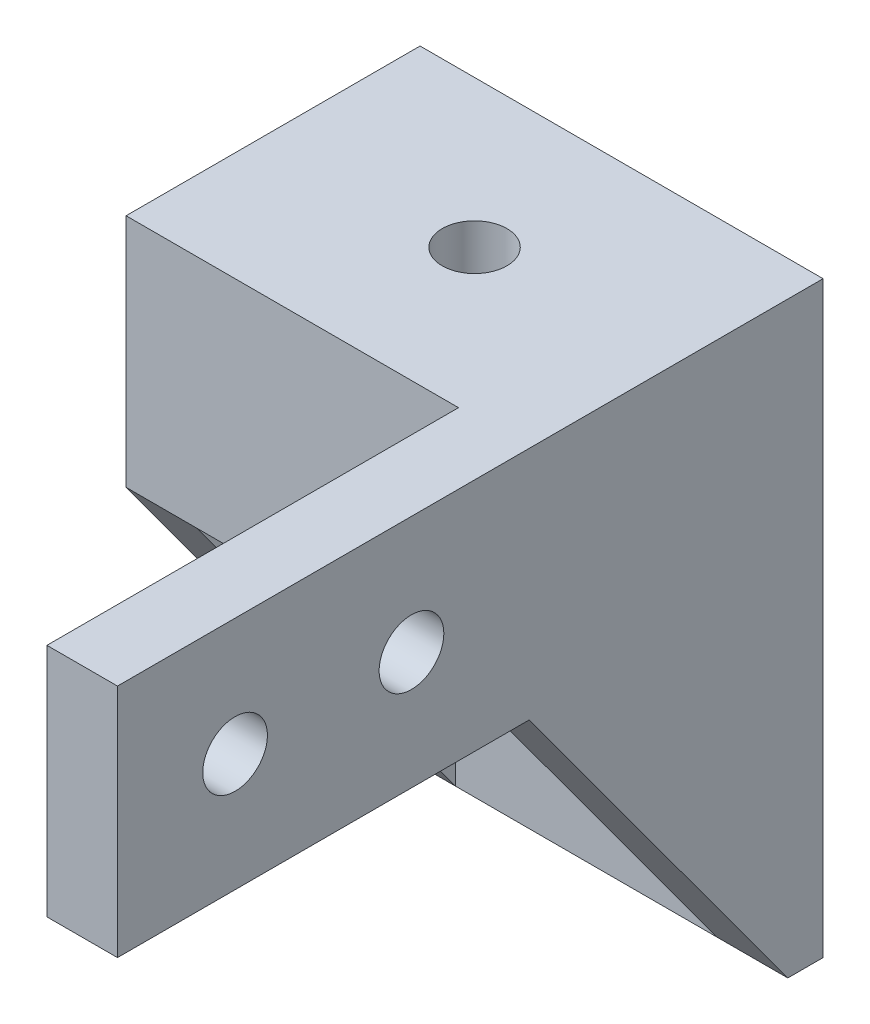
SolidWorks part; units mm, degrees
ref_plane "Front" through (0, 0, 0) normal (0, 0, 1) x (1, 0, 0)
ref_plane "Top" through (0, 0, 0) normal (0, 1, 0) x (1, 0, 0)
ref_plane "Right" through (0, 0, 0) normal (1, 0, 0) x (0, 0, -1)
sketch "Sketch1" plane through (0, 0, 0) normal (0, 1, 0) x (1, 0, 0)
  line L1 (0, 0) -> (17.135, 0)
  line L2 (0, 0) -> (0, 12.5)
  line L3 (0, 12.5) -> (17.135, 12.5)
  line L4 (17.135, 0) -> (17.135, 12.5)
  dimension "D1" = 17.135
  dimension "D2" = 12.5
extrude "base" add sketch "Sketch1" along normal blind 5
sketch "Sketch2" plane through (0, 0, -12.5) normal (0, 0, -1) x (-1, 0, 0)
  line L0 (0, 5) -> (0, 0) construction
  line L1 (-17.135, 0) -> (0, 0)
  line L2 (-17.135, 0) -> (-17.135, -15)
  line L3 (-17.135, -15) -> (0, -15)
  line L4 (0, 0) -> (0, -15)
  dimension "D1" = 15
extrude "Boss-Extrude2" add sketch "Sketch2" against normal blind 1.5
sketch "Sketch3" plane through (0, 0, 0) normal (-1, 0, 0) x (0, 0, 1)
  line L0 (0, 0) -> (-11, -15)
  line L1 (-11, -15) -> (-11, 0)
  line L2 (-11, 0) -> (0, 0)
extrude "Boss-Extrude3" add sketch "Sketch3" against normal up to surface (17.135 mm away) up to face at (17.135, -3.3333, -7.8333)
sketch "Sketch4" plane through (0, 0, 0) normal (0, 0, 1) x (1, 0, 0)
  line L0 (17.135, -15) -> (0, -15) construction
  line L1 (3, 0) -> (14.135, 0)
  line L2 (3, 0) -> (3, -15)
  line L3 (3, -15) -> (14.135, -15)
  line L4 (14.135, 0) -> (14.135, -15)
  line L5 (0, 0) -> (17.135, 0) construction
  line L6 (17.135, 0) -> (17.135, -15) construction
  point P6 (8.5675, 0)
  point P9 (8.5675, 0)
  dimension "D1" = 3
extrude "Cut-Extrude1" cut sketch "Sketch4" against normal up to vertex (11 mm away) up to point (17.135, -15, -11)
sketch "Sketch5" plane through (0, 0, -11) normal (0, 0, 1) x (1, 0, 0)
  line L0 (14.135, 0) -> (3, 0) construction
  line L1 (3, -15) -> (14.135, -15) construction
  circle A0 centre (8.5675, -4) radius 2.3 construction
  circle A1 centre (8.5675, -11) radius 2.3 construction
  circle A2 centre (8.5675, -4) radius 1.375
  circle A3 centre (8.5675, -11) radius 1.375
  point P8 (8.5675, 0)
  dimension "D1" = 4.6
  dimension "D4" = 2.75
  dimension "D2" = 4
  dimension "D3" = 4
extrude "Cut-Extrude2" cut sketch "Sketch5" against normal blind 2
sketch "Sketch6" plane through (0, 5, 0) normal (0, 1, 0) x (1, 0, 0)
  line L0 (0, 12.5) -> (0, 0) construction
  line L1 (0, 0) -> (17.135, 0) construction
  circle A0 centre (8.5675, 6.25) radius 1.375
  dimension "D1" = 2.75
  dimension "D2" = 8.5675
  dimension "D3" = 6.25
extrude "Cut-Extrude3" cut sketch "Sketch6" against normal blind 5.75
sketch "Sketch7" plane through (0, 5, 0) normal (0, 1, 0) x (1, 0, 0)
  line L8 (0, 12.5) -> (0, 0)
  line L9 (0, 0) -> (17.135, 0)
  line L10 (17.135, 0) -> (17.135, 12.5)
  line L11 (17.135, 12.5) -> (0, 12.5)
  line L12 (0, 12.5) -> (0, 0)
  line L13 (0, 0) -> (17.135, 0)
  line L14 (17.135, 0) -> (17.135, 12.5)
  line L15 (17.135, 12.5) -> (0, 12.5)
  circle A0 centre (8.5675, 6.25) radius 1.375 construction
  circle A1 centre (8.5675, 6.25) radius 1.375
  dimension "D1" = 0
extrude "Boss-Extrude4" add sketch "Sketch7" along normal blind 5
sketch "Sketch8" plane through (17.135, 0, 0) normal (1, 0, 0) x (0, 0, -1)
  line L1 (0, 10) -> (-17.5, 10)
  line L2 (0, 10) -> (0, 0)
  line L3 (0, 0) -> (-17.5, 0)
  line L4 (-17.5, 10) -> (-17.5, 0)
  line L5 (-8, 5) -> (-6.5, 2.4019) construction
  line L6 (-6.5, 2.4019) -> (-3.5, 2.4019) construction
  line L7 (-3.5, 2.4019) -> (-2, 5) construction
  line L8 (-2, 5) -> (-3.5, 7.5981) construction
  line L9 (-3.5, 7.5981) -> (-6.5, 7.5981) construction
  line L10 (-6.5, 7.5981) -> (-8, 5) construction
  line L11 (-15.5, 5) -> (-14, 2.4019) construction
  line L12 (-14, 2.4019) -> (-11, 2.4019) construction
  line L13 (-11, 2.4019) -> (-9.5, 5) construction
  line L14 (-9.5, 5) -> (-11, 7.5981) construction
  line L15 (-11, 7.5981) -> (-14, 7.5981) construction
  line L16 (-14, 7.5981) -> (-15.5, 5) construction
  circle A0 centre (-5, 5) radius 1.375
  circle A1 centre (-5, 5) radius 2.5981 construction
  circle A2 centre (-12.5, 5) radius 1.375
  circle A3 centre (-12.5, 5) radius 2.5981 construction
  point P16 (0, 5)
  dimension "D1" = 2.75
  dimension "D2" = 3
  dimension "D3" = 5
  dimension "D4" = 7.5
  dimension "D5" = 5
extrude "Boss-Extrude5" add sketch "Sketch8" against normal blind 3
